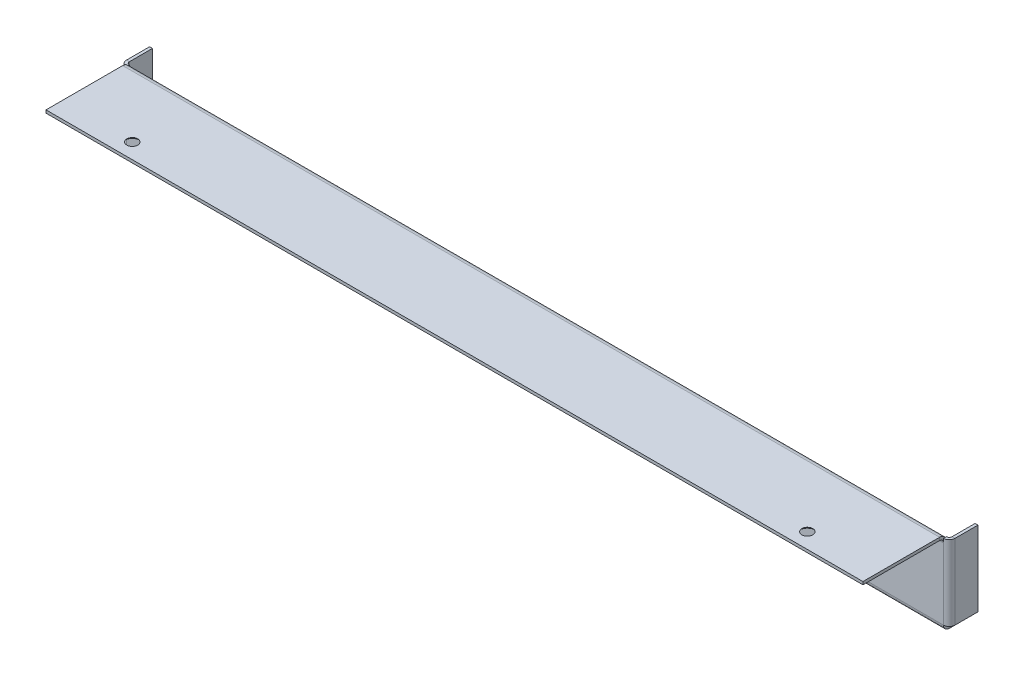
SolidWorks part; units mm, degrees
note: The reader was unsure of these and kept them because the rebuilt part matched: thickness of "Базовая кромка1", "Ребро-кромка2", "Ребро-кромка3", "Ребро-кромка4", "Ребро-кромка5", "Листовой металл1", "Листовой металл3", "Листовой металл4", "Листовой металл5", "Листовой металл6", "Листовой металл7"; flange length of "Ребро-кромка2", "Ребро-кромка3", "Ребро-кромка4", "Ребро-кромка5".
material "1060 Сплав"
ref_plane "Front" through (0, 0, 0) normal (0, 0, 1) x (1, 0, 0)
ref_plane "Top" through (0, 0, 0) normal (0, 1, 0) x (1, 0, 0)
ref_plane "Right" through (0, 0, 0) normal (1, 0, 0) x (0, 0, -1)
sketch "Эскиз1" plane through (0, 0, 0) normal (0, 0, 1) x (1, 0, 0)
  line L1 (0, 0) -> (426, 0)
  line L2 (0, 0) -> (0, 39.2)
  line L3 (0, 39.2) -> (426, 39.2)
  line L4 (426, 0) -> (426, 39.2)
  dimension "D1" = 39.2
  dimension "D2" = 426
base flange "Базовая кромка1" sketch "Эскиз1" thickness 1.5 reverse thickness direction no parameters "D1"=2
edge flange "Ребро-кромка2" sketch "Эскиз18" flange angle 90 flange length 15 flange position bend outside bend radius 1.5 thickness 1.5 relief rectangular parameters "D6"=10, "D8"=1
sketch "Эскиз18" plane through (0, 0, -1.5) normal (-1, 0, 0) x (0, 1, 0)
  line L0 (39.2, 0) -> (0, 0) construction
  line L1 (39.2, 0) -> (0, 0)
  line L2 (0, 0) -> (0, 13.5)
  line L3 (0, 13.5) -> (39.2, 13.5)
  line L4 (39.2, 13.5) -> (39.2, 0)
bend "EdgeBend4" bend radius 1.5 bend angle 90 parameters "D5"=4
edge flange "Ребро-кромка3" sketch "Эскиз21" flange angle 90 flange length 15 flange position bend outside bend radius 1.5 thickness 1.5 relief rectangular parameters "D6"=10
sketch "Эскиз21" plane through (0, 0, -1.5) normal (0, -1, 0) x (-1, 0, 0)
  line L2 (-426, 0) -> (-426, 13.5)
  line L3 (-426, 13.5) -> (0, 13.5)
  line L4 (0, 13.5) -> (0, 0)
  line L7 (0, 0) -> (-426, 0) construction
  line L8 (0, 0) -> (-426, 0)
bend "EdgeBend5" bend radius 1.5 bend angle 90 parameters "D5"=5
edge flange "Ребро-кромка4" sketch "Эскиз24" flange angle 90 flange length 15 flange position bend outside bend radius 1.5 thickness 1.5 relief rectangular parameters "D6"=10
sketch "Эскиз24" plane through (426, 0, -1.5) normal (1, 0, 0) x (0, -1, 0)
  line L0 (0, 0) -> (-39.2, 0) construction
  line L1 (0, 0) -> (-39.2, 0)
  line L2 (-39.2, 0) -> (-39.2, 13.5)
  line L3 (-39.2, 13.5) -> (0, 13.5)
  line L4 (0, 13.5) -> (0, 0)
bend "EdgeBend6" bend radius 1.5 bend angle 90 parameters "D5"=6
edge flange "Ребро-кромка5" sketch "Эскиз27" flange angle 90 flange length 43.5 flange position material outside bend radius 2 thickness 1.5 relief none parameters "D6"=10
sketch "Эскиз27" plane through (0, 39.2, 0) normal (0, 1, 0) x (-1, 0, 0)
  line L2 (-426, 0) -> (-426, 42)
  line L3 (-426, 42) -> (0, 42)
  line L4 (0, 42) -> (0, 0)
  line L5 (-426, 0) -> (0, 0) construction
  line L6 (-426, 0) -> (0, 0)
bend "EdgeBend7" bend radius 2 bend angle 90 parameters "D5"=7
sketch "Эскиз28" plane through (0, 39.2, 0) normal (0, -1, 0) x (1, 0, 0)
  line L0 (0, 2) -> (0, 42) construction
  line L1 (0, 42) -> (426, 42) construction
  line L2 (426, 42) -> (426, 2) construction
  circle A0 centre (37, 34) radius 2.3
  circle A1 centre (389, 34) radius 2.3
  dimension "D1" = 4.6
  dimension "D2" = 37
  dimension "D3" = 8
  dimension "D4" = 4.6
  dimension "D5" = 37
  dimension "D6" = 8
extrude "Вырез-Вытянуть1" cut sketch "Эскиз28" against normal through all normal cut yes
chamfer "Фаска1" distance 2.05 angle 45 2 edges at (389, 39.2, 31.7) (37, 39.2, 31.7)
sketch "Сгиб-Линии1" [suppressed] plane through (0, 0, 0) normal (0, 1, 0) x (1, 0, 0)
sketch "Граничная рамка1" [suppressed] plane through (0, 0, 0) normal (0, 1, 0) x (1, 0, 0)
sheet metal parameters "Листовой металл1" thickness 1.5 parameters "D1"=2
flat pattern "Развертка1" [suppressed]
sketch "Сгиб-Линии2" plane through (0, 0, 0) normal (0, 1, 0) x (1, 0, 0)
sketch3d "Граничная рамка2" [suppressed]
  line L0 (0, 0, 0) -> (-432, 0, 0) construction
  line L1 (0, 43.7, 0) -> (-432, 43.7, 0) construction
  line L2 (0, 0, 0) -> (0, 43.7, 0) construction
  line L3 (-432, 0, 0) -> (-432, 43.7, 0) construction
sheet metal parameters "Листовой металл3" thickness 1.5 parameters "D1"=2, "D7"=2
flat pattern "Развертка1"
sketch "Сгиб-Линии2" plane through (0, 0, 0) normal (0, 0, 1) x (1, 0, 0)
  line L0 (432, 46.0562) -> (0, 46.0562) construction
  line L1 (432, 46.0562) -> (0, 46.0562) construction
  line L2 (-2.3562, 43.7) -> (-2.3562, 0) construction
  line L5 (-2.3562, 43.7) -> (-2.3562, 0) construction
sketch3d "Граничная рамка2" [suppressed]
  line L0 (-15.7124, 0, 0) -> (432, 0, 0) construction
  line L1 (-15.7124, 88.4124, 0) -> (432, 88.4124, 0) construction
  line L2 (-15.7124, 0, 0) -> (-15.7124, 88.4124, 0) construction
  line L3 (432, 0, 0) -> (432, 88.4124, 0) construction
bend of the flat pattern "Плоское состояние-<EdgeBend4>1"
sheet metal parameters "Листовой металл4" thickness 1.5 parameters "D1"=2, "D7"=2
flat pattern "Развертка1"
sketch "Сгиб-Линии2" plane through (0, 0, 0) normal (0, 0, 1) x (1, 0, 0)
  line L0 (432, 46.0562) -> (0, 46.0562) construction
  line L1 (432, 46.0562) -> (0, 46.0562) construction
  line L2 (-2.3562, 43.7) -> (-2.3562, 0) construction
  line L3 (0, -2.3562) -> (432, -2.3562) construction
  line L4 (0, -2.3562) -> (432, -2.3562) construction
  line L5 (-2.3562, 43.7) -> (-2.3562, 0) construction
sketch3d "Граничная рамка2" [suppressed]
  line L0 (-15.7124, -15.7124, 0) -> (432, -15.7124, 0) construction
  line L1 (-15.7124, 88.4124, 0) -> (432, 88.4124, 0) construction
  line L2 (-15.7124, -15.7124, 0) -> (-15.7124, 88.4124, 0) construction
  line L3 (432, -15.7124, 0) -> (432, 88.4124, 0) construction
bend of the flat pattern "Плоское состояние-<EdgeBend4>1"
bend of the flat pattern "Плоское состояние-<EdgeBend5>1"
sheet metal parameters "Листовой металл5" thickness 1.5 parameters "D1"=2, "D7"=2
flat pattern "Развертка1"
sketch "Сгиб-Линии2" plane through (0, 0, 0) normal (0, 0, 1) x (1, 0, 0)
  line L2 (-1.7671, 40.7) -> (-1.7671, 0) construction
  line L3 (0, -1.7671) -> (426, -1.7671) construction
  line L4 (0, -1.7671) -> (426, -1.7671) construction
  line L5 (-1.7671, 40.7) -> (-1.7671, 0) construction
  line L6 (427.7671, 0) -> (427.7671, 40.7) construction
  line L7 (427.7671, 0) -> (427.7671, 40.7) construction
sketch3d "Граничная рамка2" [suppressed]
  line L0 (-15.5343, -15.5343, 0) -> (441.5343, -15.5343, 0) construction
  line L1 (-15.5343, 40.7, 0) -> (441.5343, 40.7, 0) construction
  line L2 (-15.5343, -15.5343, 0) -> (-15.5343, 40.7, 0) construction
  line L3 (441.5343, -15.5343, 0) -> (441.5343, 40.7, 0) construction
bend of the flat pattern "Плоское состояние-<EdgeBend4>1"
bend of the flat pattern "Плоское состояние-<EdgeBend5>1"
bend of the flat pattern "Плоское состояние-<EdgeBend6>1"
sheet metal parameters "Листовой металл6" thickness 1.5 parameters "D1"=2, "D7"=2
flat pattern "Развертка1"
sketch "Сгиб-Линии2" plane through (0, 0, 0) normal (0, 0, 1) x (1, 0, 0)
  line L0 (426, 39.3598) -> (0, 39.3598) construction
  line L1 (426, 39.3598) -> (0, 39.3598) construction
  line L2 (-1.7671, 39.2) -> (-1.7671, 0) construction
  line L3 (0, -1.7671) -> (426, -1.7671) construction
  line L4 (0, -1.7671) -> (426, -1.7671) construction
  line L5 (-1.7671, 39.2) -> (-1.7671, 0) construction
  line L6 (427.7671, 0) -> (427.7671, 39.2) construction
  line L7 (427.7671, 0) -> (427.7671, 39.2) construction
sketch3d "Граничная рамка2" [suppressed]
  line L0 (-15.5343, -15.5343, 0) -> (441.5343, -15.5343, 0) construction
  line L1 (-15.5343, 81.5197, 0) -> (441.5343, 81.5197, 0) construction
  line L2 (-15.5343, -15.5343, 0) -> (-15.5343, 81.5197, 0) construction
  line L3 (441.5343, -15.5343, 0) -> (441.5343, 81.5197, 0) construction
bend of the flat pattern "Плоское состояние-<EdgeBend4>1"
bend of the flat pattern "Плоское состояние-<EdgeBend5>1"
bend of the flat pattern "Плоское состояние-<EdgeBend6>1"
bend of the flat pattern "Плоское состояние-<EdgeBend7>1"
sheet metal parameters "Листовой металл7" thickness 1.5 parameters "D1"=2, "D7"=2
flat pattern "Развертка1"
sketch "Сгиб-Линии2" plane through (0, 0, 0) normal (0, 0, 1) x (1, 0, 0)
  line L0 (426, 39.3598) -> (0, 39.3598) construction
  line L1 (426, 39.3598) -> (0, 39.3598) construction
  line L2 (-1.7671, 39.2) -> (-1.7671, 0) construction
  line L3 (0, -1.7671) -> (426, -1.7671) construction
  line L4 (0, -1.7671) -> (426, -1.7671) construction
  line L5 (-1.7671, 39.2) -> (-1.7671, 0) construction
  line L6 (427.7671, 0) -> (427.7671, 39.2) construction
  line L7 (427.7671, 0) -> (427.7671, 39.2) construction
sketch3d "Граничная рамка2" [suppressed]
  line L0 (-15.5343, -15.5343, 0) -> (441.5343, -15.5343, 0) construction
  line L1 (-15.5343, 81.5197, 0) -> (441.5343, 81.5197, 0) construction
  line L2 (-15.5343, -15.5343, 0) -> (-15.5343, 81.5197, 0) construction
  line L3 (441.5343, -15.5343, 0) -> (441.5343, 81.5197, 0) construction
bend of the flat pattern "Плоское состояние-<EdgeBend4>1"
bend of the flat pattern "Плоское состояние-<EdgeBend5>1"
bend of the flat pattern "Плоское состояние-<EdgeBend6>1"
bend of the flat pattern "Плоское состояние-<EdgeBend7>1"
